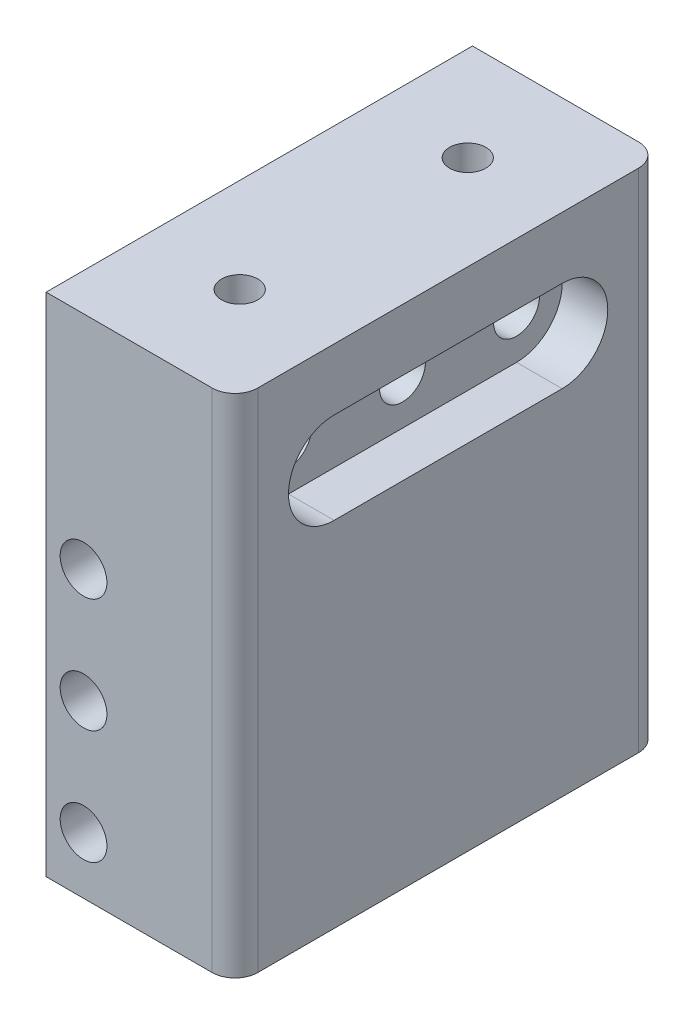
SolidWorks part; units mm, degrees
material "PET"
ref_plane "Front Plane" through (0, 0, 0) normal (0, 0, 1) x (1, 0, 0)
ref_plane "Top Plane" through (0, 0, 0) normal (0, 1, 0) x (1, 0, 0)
ref_plane "Right Plane" through (0, 0, 0) normal (1, 0, 0) x (0, 0, -1)
sketch "Sketch1" plane through (0, 0, 0) normal (0, 1, 0) x (1, 0, 0)
  line L1 (-10.5156, -23.7427) -> (10.5156, -23.7427)
  line L2 (-10.5156, -23.7427) -> (-10.5156, 23.7426)
  line L3 (-10.5156, 23.7426) -> (10.5156, 23.7426)
  line L4 (10.5156, -23.7427) -> (10.5156, 23.7426)
  line L5 (-10.5156, -23.7427) -> (10.5156, 23.7426) construction
  line L6 (-10.5156, 23.7426) -> (10.5156, -23.7427) construction
  point P0 (0, 0)
  dimension "D1" = 21.0312
  dimension "D2" = 47.4853
extrude "Boss-Extrude1" add sketch "Sketch1" along normal mid plane 50.8
sketch "Sketch2" plane through (0, 0, 23.7427) normal (0, 0, 1) x (1, 0, 0)
  line L5 (-10.5156, 25.4) -> (10.5156, 25.4) construction
  circle A1 centre (-6.35, -6.35) radius 2.6035
  circle A2 centre (-6.35, 6.35) radius 2.6035
  circle A3 centre (-6.35, -19.05) radius 2.6035
  point P10 (0, 0)
  dimension "D3" = 19.05
  dimension "D1" = 16.8656
  dimension "D2" = 5.207
  dimension "D4" = 12.7
  dimension "D5" = 12.7
extrude "Cut-Extrude1" cut sketch "Sketch2" against normal through all
sketch "Sketch4" plane through (10.5156, 0, 0) normal (1, 0, 0) x (0, 0, -1)
  line L0 (-23.7427, 25.4) -> (23.7426, 25.4) construction
  circle A0 centre (-12.7, 19.05) radius 2.5527
  circle A1 centre (12.7, 19.05) radius 2.5527
  circle A2 centre (0, 19.05) radius 2.5527
  dimension "D5" = 5.1054
  dimension "D1" = 6.35
  dimension "D3" = 12.7
  dimension "D4" = 12.7
extrude "Cut-Extrude3" cut sketch "Sketch4" against normal through all
fillet "Fillet1" radius 2.54 2 edges at (10.5156, 0, 23.7427) (10.5156, 0, -23.7426)
sketch "Sketch7" plane through (10.5156, 0, 0) normal (1, 0, 0) x (0, 0, -1)
  line L0 (-12.7, 19.05) -> (12.7, 19.05) construction
  line L1 (-12.7, 24.13) -> (12.7, 24.13)
  line L2 (-12.7, 13.97) -> (12.7, 13.97)
  arc A0 (-12.7, 24.13) -> (-12.7, 13.97) centre (-12.7, 19.05) ccw
  arc A1 (12.7, 13.97) -> (12.7, 24.13) centre (12.7, 19.05) ccw
  point P4 (0, 19.05)
  dimension "D1" = 5.08
extrude "Cut-Extrude5" cut sketch "Sketch7" against normal blind 5.08
sketch "Sketch8" plane through (0, 25.4, 0) normal (0, 1, 0) x (1, 0, 0)
  line L4 (-10.5156, -23.7427) -> (7.9756, -23.7427)
  line L5 (10.5156, -21.2026) -> (10.5156, 21.2026)
  line L6 (7.9756, 23.7426) -> (-10.5156, 23.7426)
  line L7 (-10.5156, 23.7426) -> (-10.5156, -23.7427)
  line L8 (-10.5156, -23.7427) -> (7.9756, -23.7427)
  line L9 (10.5156, -21.2026) -> (10.5156, 21.2026)
  line L10 (7.9756, 23.7426) -> (-10.5156, 23.7426)
  line L11 (-10.5156, 23.7426) -> (-10.5156, -23.7427)
  arc A4 (7.9756, -23.7427) -> (10.5156, -21.2026) centre (7.9756, -21.2026) ccw
  arc A5 (10.5156, 21.2026) -> (7.9756, 23.7426) centre (7.9756, 21.2026) ccw
  arc A8 (7.9756, -23.7427) -> (10.5156, -21.2026) centre (7.9756, -21.2026) ccw
  arc A9 (10.5156, 21.2026) -> (7.9756, 23.7426) centre (7.9756, 21.2026) ccw
  dimension "D1" = 0
extrude "Boss-Extrude2" add sketch "Sketch8" along normal blind 5.588
sketch "Sketch9" plane through (0, 30.988, 0) normal (0, 1, 0) x (1, 0, 0)
  line L0 (-10.5156, 0) -> (10.5156, 0) construction
  line L1 (-10.5156, 23.7426) -> (-10.5156, -23.7427) construction
  line L2 (10.5156, -21.2026) -> (10.5156, 21.2026) construction
  circle A0 centre (0, 12.7) radius 2.0193
  circle A2 centre (0, -12.7) radius 2.0193
  dimension "D2" = 4.0386
  dimension "D1" = 12.7
  dimension "D3" = 10.5156
extrude "Cut-Extrude6" cut sketch "Sketch9" against normal blind 5.08
